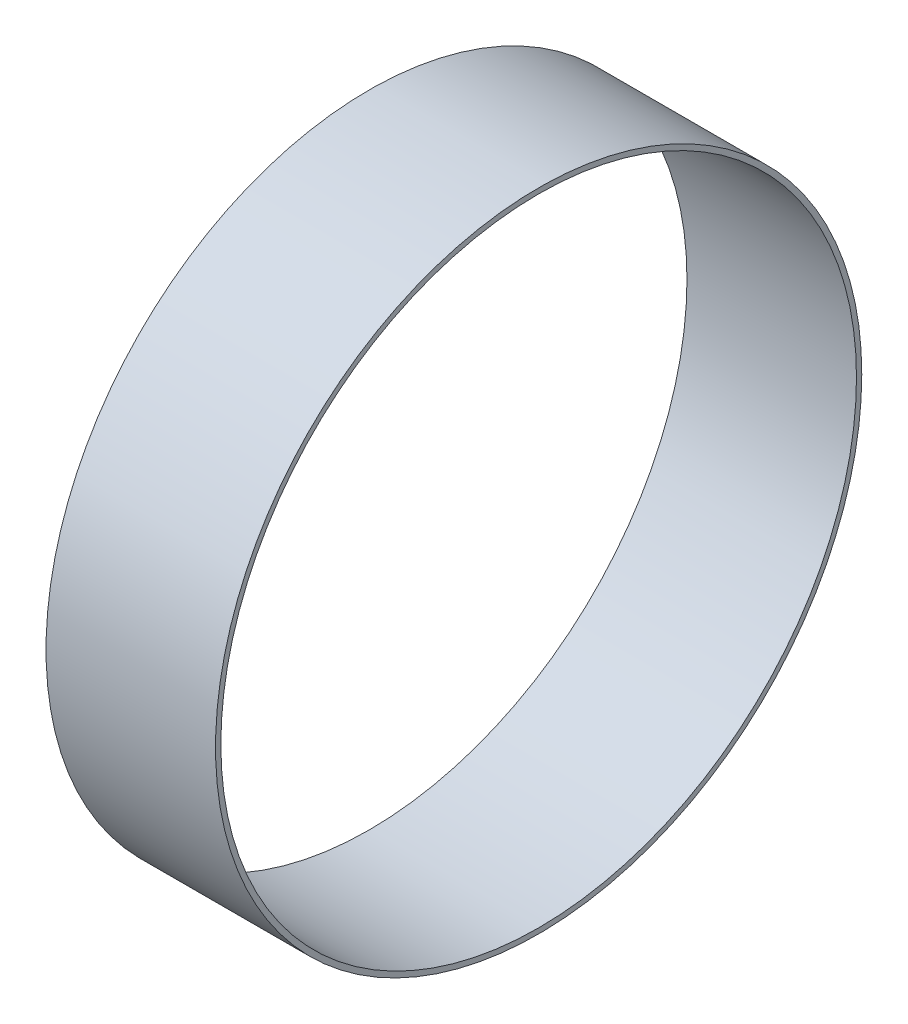
SolidWorks part; units mm, degrees
material "6061 Alloy"
ref_plane "Front Plane" through (0, 0, 0) normal (0, 0, 1) x (1, 0, 0)
ref_plane "Top Plane" through (0, 0, 0) normal (0, 1, 0) x (1, 0, 0)
ref_plane "Right Plane" through (0, 0, 0) normal (1, 0, 0) x (0, 0, -1)
sketch "Sketch1" plane through (0, 0, 0) normal (1, 0, 0) x (0, 0, -1)
  line L0 (-190.5, 0) -> (-193.675, 0) construction
  circle A0 centre (0, 0) radius 193.675
  circle A1 centre (0, 0) radius 190.5
  dimension "D2" = 381
  dimension "D1" = 3.175
extrude "Boss-Extrude1" add sketch "Sketch1" along normal blind 101.6
